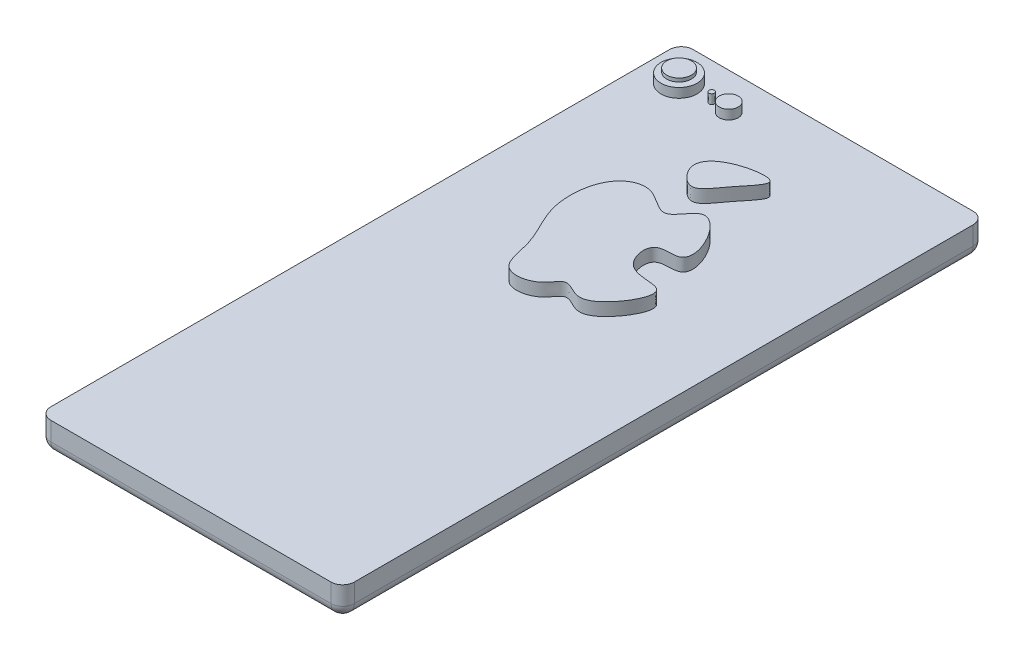
SolidWorks part; units mm, degrees
ref_plane "Front Plane" through (0, 0, 0) normal (0, 0, 1) x (1, 0, 0)
ref_plane "Top Plane" through (0, 0, 0) normal (0, 1, 0) x (1, 0, 0)
ref_plane "Right Plane" through (0, 0, 0) normal (1, 0, 0) x (0, 0, -1)
sketch "Sketch1" plane through (0, 0, 0) normal (0, 1, 0) x (1, 0, 0)
  line L0 (-43.1028, 37.5444) -> (-43.1028, -97.007)
  line L1 (-40.5628, -99.547) -> (20.3541, -99.547)
  line L2 (22.8941, -97.007) -> (22.8941, 37.5444)
  line L3 (20.3541, 40.0844) -> (-40.5628, 40.0844)
  arc A0 (-43.1028, -97.007) -> (-40.5628, -99.547) centre (-40.5628, -97.007) ccw
  arc A1 (20.3541, -99.547) -> (22.8941, -97.007) centre (20.3541, -97.007) ccw
  arc A2 (22.8941, 37.5444) -> (20.3541, 40.0844) centre (20.3541, 37.5444) ccw
  arc A3 (-43.1028, 37.5444) -> (-40.5628, 40.0844) centre (-40.5628, 37.5444) cw
  dimension "D1" = 2.54
extrude "Boss-Extrude1" add sketch "Sketch1" along normal blind 6.604
sketch "Sketch2" plane through (0, 6.604, 0) normal (0, 1, 0) x (1, 0, 0)
  circle A0 centre (-35.6631, 32.1385) radius 3.9195
  circle A1 centre (-28.5455, 32.1385) radius 0.5664
  circle A2 centre (-24.8513, 32.1385) radius 2.0652
extrude "Boss-Extrude2" add sketch "Sketch2" along normal blind 2.032
sketch "Sketch3" plane through (0, 0, 0) normal (0, -1, 0) x (-1, 0, 0)
  line L0 (40.5628, 24.5396) -> (-20.3541, 24.5396)
  line L1 (-20.3541, 24.5396) -> (-20.3541, -82.3211)
  line L2 (-20.3541, -82.3211) -> (40.5628, -82.3211)
  line L3 (40.5628, 24.5396) -> (40.5628, -82.3211)
  line L4 (-22.8941, -97.007) -> (-22.8941, 37.5444) construction
  line L5 (43.1028, 37.5444) -> (43.1028, -97.007) construction
  line L6 (40.5628, -99.547) -> (-20.3541, -99.547) construction
  line L7 (-20.3541, 40.0844) -> (40.5628, 40.0844) construction
  dimension "D1" = 2.54
  dimension "D2" = 2.54
  dimension "D3" = 17.2259
  dimension "D4" = 15.5448
extrude "Cut-Extrude1" cut sketch "Sketch3" against normal blind 2.032
sketch "Sketch4" plane through (0, 0, 0) normal (0, -1, 0) x (-1, 0, 0)
  line L0 (-22.8941, -97.007) -> (-22.8941, 37.5444) construction
  circle A0 centre (8.8559, -90.2158) radius 5.3671
  dimension "D1" = 31.75
extrude "Cut-Extrude2" cut sketch "Sketch4" against normal blind 1.27
sketch "Sketch5" plane through (0, 0, 0) normal (0, -1, 0) x (-1, 0, 0)
  line L0 (12.7322, 31.4738) -> (1.226, 31.4738)
  line L1 (1.226, 31.4738) -> (1.226, 32.7438)
  line L2 (1.226, 32.7438) -> (12.7322, 32.7438)
  line L3 (12.7322, 32.7438) -> (12.7322, 31.4738)
  line L4 (40.5628, 24.5396) -> (-20.3541, 24.5396) construction
  line L5 (-20.3541, 40.0844) -> (40.5628, 40.0844) construction
  line L6 (-22.8941, -97.007) -> (-22.8941, 37.5444) construction
  circle A0 centre (-2.8881, 31.3976) radius 1.27
  circle A1 centre (8.1701, 34.6498) radius 1.2282
  dimension "D1" = 2.54
  dimension "D5" = 6.858
  dimension "D6" = 10.1102
  dimension "D7" = 5.4346
  dimension "D8" = 31.0642
  dimension "D2" = 11.5062
  dimension "D3" = 1.27
  dimension "D4" = 6.9342
extrude "Cut-Extrude3" cut sketch "Sketch5" against normal blind 1.016
fillet "Fillet1" radius 2.54 8 edges at (-42.3589, 0, -39.3405) (-10.1044, 0, -40.0844) (22.1501, 0, -39.3405) (22.1501, 0, 98.803) (-10.1044, 0, 99.547) (-42.3589, 0, 98.803) (22.8941, 0, 29.7313) (-43.1028, 0, 29.7313)
sketch "Sketch7" plane through (0, 6.604, 0) normal (0, 1, 0) x (1, 0, 0)
  circle A0 centre (-35.7271, 32.2309) radius 2.9444
extrude "Cut-Extrude4" cut sketch "Sketch7" against normal blind 2.54
sketch "Sketch8" plane through (0, 8.636, 0) normal (0, 1, 0) x (1, 0, 0)
  circle A0 centre (-35.8074, 32.2935) radius 2.6844
extrude "Boss-Extrude3" add sketch "Sketch8" along normal blind 0.762
sketch "Sketch9" plane through (0, 6.604, 0) normal (0, 1, 0) x (1, 0, 0)
  spline S0 degree 3 poles (-10.3733, -24.2618) (-8.0071, -19.2406) (-3.9223, -22.5599) (1.3607, -19.7879) (6.835, -9.5952) (-4.5313, -12.4485) (-6.4409, -2.4924) (4.9014, -5.2505) (-4.8648, 12.659) (-9.6016, 0.7852) (-14.7583, 6.8895) (-23.2345, 5.3131) (-24.9982, -7.8821) (-18.8176, -15.3698) (-18.0236, -25.4287) (-10.3733, -24.2618) (-8.0071, -19.2406) (-3.9223, -22.5599) knots -0.15928 -0.094549 -0.031399 0 0.035105 0.079769 0.164437 0.236107 0.292319 0.337297 0.45144 0.503272 0.568003 0.603803 0.733112 0.84072 0.905451 0.968601 1 1.035105 1.079769 1.164437 only from (-7.8006, -20.4009) to (-7.8006, -20.4009)
  spline S1 degree 3 poles (-2.1867, 21.7544) (-11.4139, 21.1391) (-18.362, 16.5573) (-11.7013, 9.3349) (-8.2692, 15.539) (-2.1867, 21.7544) (-11.4139, 21.1391) (-18.362, 16.5573) knots -0.563557 -0.363594 -0.163494 0 0.273457 0.436443 0.636406 0.836506 1 1.273457 1.436443 1.636406 only from (-9.6436, 20.8372) to (-9.6436, 20.8372)
extrude "Boss-Extrude4" add sketch "Sketch9" along normal blind 2.794
